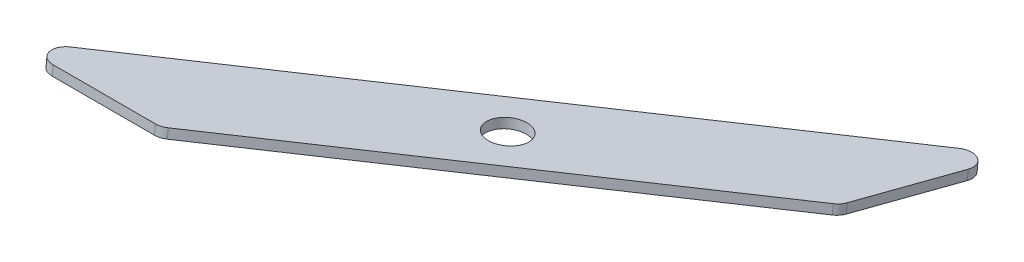
SolidWorks part; units mm, degrees
material "Plain Carbon Steel"
ref_plane "Front Plane" through (0, 0, 0) normal (0, 0, 1) x (1, 0, 0)
ref_plane "Top Plane" through (0, 0, 0) normal (0, 1, 0) x (1, 0, 0)
ref_plane "Right Plane" through (0, 0, 0) normal (1, 0, 0) x (0, 0, -1)
ref_axis "Axis1" through (322.9021, -198.3148, 90.0878) along (-0.2127, 0.0964, 0.9723)
ref_axis "Axis2" through (-329.7721, -201.4292, 58.6842) along (0.2127, 0.0964, 0.9723)
ref_axis "Axis3" through (201.261, -142.7141, 653.3483) along (-1, 0, 0)
ref_plane "Plane1" through (0, -189.2291, 18.6231) normal (0, 0.9952, -0.0979) x (1, 0, 0)
ref_plane "Plane2" through (0, -201.8681, 19.8669) normal (0, -0.9952, 0.0979) x (-1, 0, 0)
sketch "Sketch1" plane through (0, -201.8681, 19.8669) normal (0, -0.9952, 0.0979) x (-1, 0, 0)
  line L0 (-210.8189, -585.1016) -> (-147.3502, -636.2399)
  line L1 (-322.9021, -70.2419) -> (-206.8084, -603.5238) construction
  line L2 (-201.261, -636.2399) -> (201.2079, -636.2399) construction
  line L3 (-147.3502, -636.2399) -> (-122.0477, -636.2399)
  line L4 (-122.0477, -636.2399) -> (-216.2011, -560.3782)
  line L5 (-216.2011, -560.3782) -> (-210.8189, -585.1016)
  line L6 (-213.51, -572.7399) -> (-134.699, -636.2399) construction
  line L7 (-216.2011, -560.3782) -> (-147.3502, -636.2399) construction
  line L8 (-122.0477, -636.2399) -> (-210.8189, -585.1016) construction
  circle A0 centre (-174.1045, -604.4899) radius 3.2639
  dimension "D2" = 6.5278
  dimension "D3" = 31.75
  dimension "D1" = 15.875
extrude "Boss-Extrude1" add sketch "Sketch1" along normal blind 1.5875
fillet "Fillet1" radius 2.54 4 edges at (122.0477, -140.3433, 653.1256) (147.3502, -140.3433, 653.1256) (210.8189, -145.3519, 602.2332) (216.2011, -147.7733, 577.6286)
